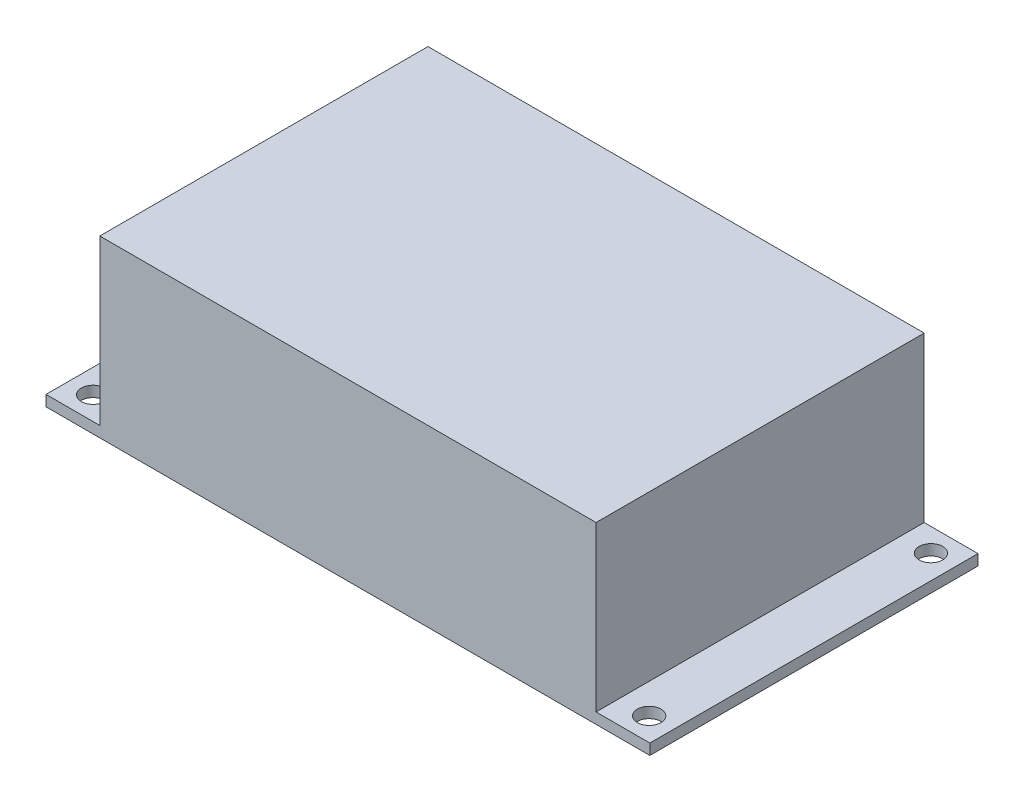
SolidWorks part; units mm, degrees
ref_plane "前视" through (0, 0, 0) normal (0, 0, 1) x (1, 0, 0)
ref_plane "上视" through (0, 0, 0) normal (0, 1, 0) x (1, 0, 0)
ref_plane "右视" through (0, 0, 0) normal (1, 0, 0) x (0, 0, -1)
sketch "草图1" plane through (0, 0, 0) normal (0, 1, 0) x (1, 0, 0)
  line L0 (-106.8768, 0) -> (85.3196, 0) construction
  line L1 (-44.9, 24.4) -> (44.9, 24.4)
  line L2 (-44.9, 24.4) -> (-44.9, -24.4)
  line L3 (-44.9, -24.4) -> (44.9, -24.4)
  line L4 (44.9, 24.4) -> (44.9, -24.4)
  line L5 (0, 69.3465) -> (0, -69.6063) construction
  dimension "D1" = 89.8
  dimension "D2" = 48.8
extrude "凸台-拉伸1" add sketch "草图1" along normal blind 1.6
sketch "草图2" plane through (0, 1.6, 0) normal (0, 1, 0) x (1, 0, 0)
  line L0 (-49.3624, 0) -> (61.9395, 0) construction
  line L1 (0, 27.7214) -> (0, -30.4894) construction
  circle A0 centre (-41.35, 20.95) radius 1.75
  circle A1 centre (-41.35, -20.95) radius 1.75
  circle A2 centre (41.35, -20.95) radius 1.75
  circle A3 centre (41.35, 20.95) radius 1.75
  dimension "D3" = 3.5
  dimension "D1" = 82.7
  dimension "D2" = 41.9
extrude "切除-拉伸1" cut sketch "草图2" against normal blind 1.6
sketch "草图3" plane through (0, 1.6, 0) normal (0, 1, 0) x (1, 0, 0)
  line L0 (44.9, 24.4) -> (-44.9, 24.4) construction
  line L1 (-36.9, 24.4) -> (36.9, 24.4)
  line L2 (-36.9, 24.4) -> (-36.9, -24.4)
  line L3 (-36.9, -24.4) -> (36.9, -24.4)
  line L4 (36.9, 24.4) -> (36.9, -24.4)
  line L5 (-44.9, -24.4) -> (44.9, -24.4) construction
  line L6 (0, 46.5122) -> (0, -44.0401) construction
  line L7 (-44.9, 24.4) -> (-44.9, -24.4) construction
  dimension "D1" = 8
extrude "凸台-拉伸2" add sketch "草图3" along normal offset from surface (24.4 mm away) 26 up to face at (41.35, 0, -22.7)
